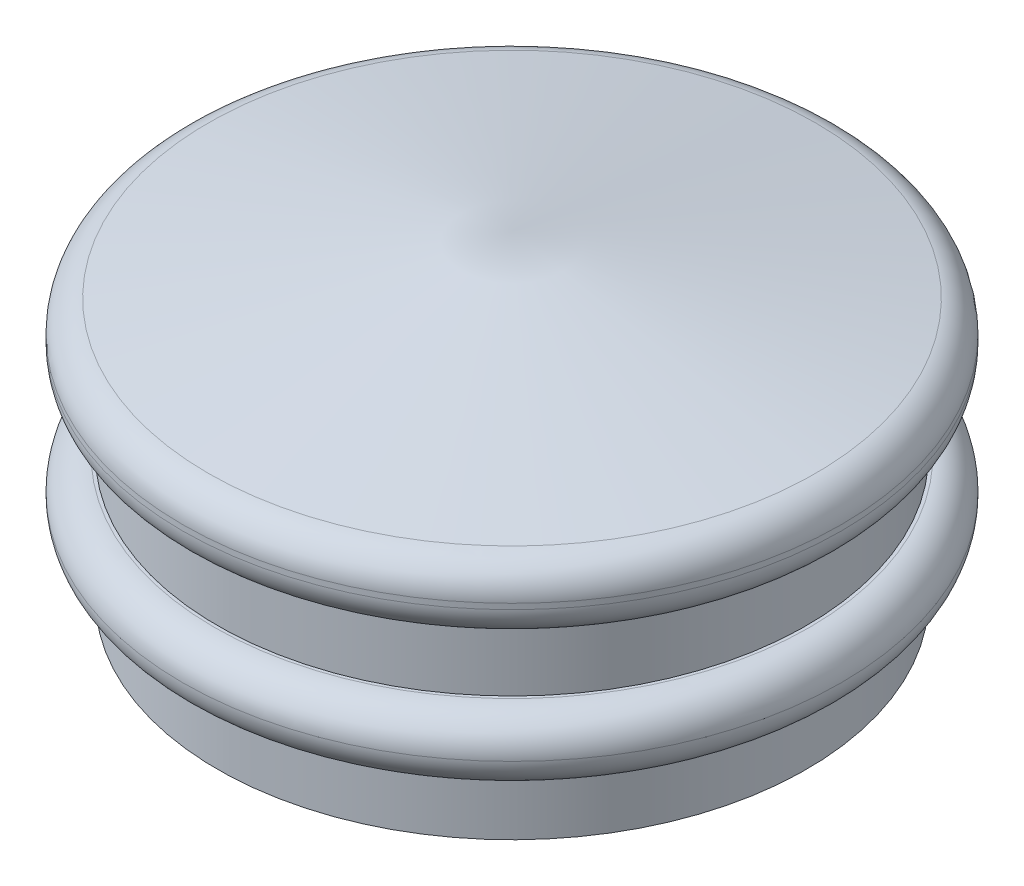
SolidWorks part; units mm, degrees
ref_plane "Front" through (0, 0, 0) normal (0, 0, 1) x (1, 0, 0)
ref_plane "Top" through (0, 0, 0) normal (0, 1, 0) x (1, 0, 0)
ref_plane "Right" through (0, 0, 0) normal (1, 0, 0) x (0, 0, -1)
sketch "Sketch1" plane through (0, 0, 0) normal (0, 0, 1) x (1, 0, 0)
  line L1 (0, 7.5) -> (-7.75, 6.0182)
  line L2 (-7.75, 6.0182) -> (-7.75, 4.5182)
  line L3 (-7.75, 4.5182) -> (-6.9274, 4.5182)
  line L4 (-6.9274, 4.5182) -> (-6.9274, 2.9278)
  line L5 (-6.9274, 2.9278) -> (-7.75, 2.9278)
  line L6 (-7.75, 2.9278) -> (-7.75, 1.4278)
  line L8 (-7.75, 1.4278) -> (-6.9274, 1.4278)
  line L9 (-6.9274, 1.4278) -> (-6.9274, 0)
  line L10 (-6.9274, 0) -> (-5.1363, 0)
  line L11 (-5.1363, 0) -> (-3.1267, 1.4278)
  line L12 (-3.1267, 1.4278) -> (-3.1267, 4.7)
  line L13 (-3.1267, 4.7) -> (0, 4.7)
  line L14 (0, 0) -> (0, 4.7) construction
  line L15 (0, 4.7) -> (0, 7.5)
  point P2 (-6.9274, 2.9278)
  point P16 (0.1661, 5.3501)
  point P17 (-3.7383, 0)
  point P18 (-3.1267, 1.4278)
  point P19 (-5.1363, 0)
  dimension "D1" = 1.5
  dimension "D2" = 7.5
  dimension "D3" = 4.7
  dimension "D4" = 7.75
revolve "Revolve1" add sketch "Sketch1" angle 360 about L14
fillet "Fillet1" radius 0.75 4 edges at (0, 6.0182, -7.75) (0, 4.5182, -7.75) (0, 2.9278, -7.75) (0, 1.4278, -7.75)
